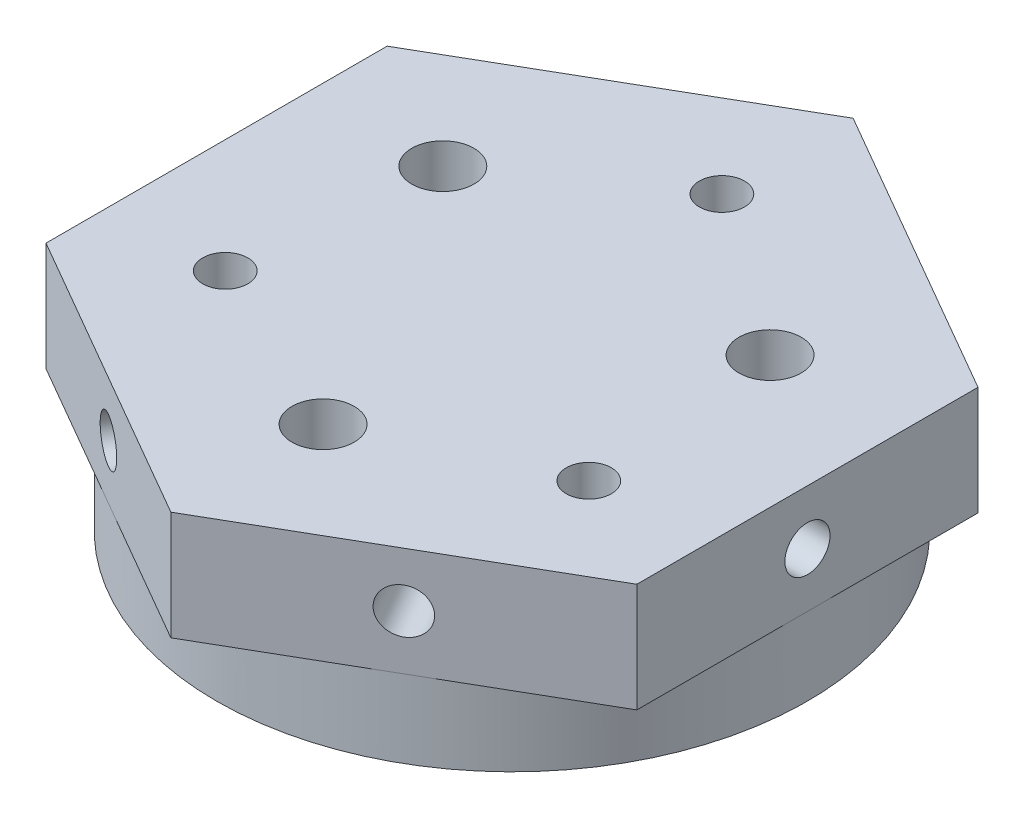
SolidWorks part; units mm, degrees
ref_plane "前视基准面" through (0, 0, 0) normal (0, 0, 1) x (1, 0, 0)
ref_plane "上视基准面" through (0, 0, 0) normal (0, 1, 0) x (1, 0, 0)
ref_plane "右视基准面" through (0, 0, 0) normal (1, 0, 0) x (0, 0, -1)
sketch "草图1" plane through (0, 0, 0) normal (0, 1, 0) x (1, 0, 0)
  line L0 (0, 0) -> (0, 33.3478) construction
  line L1 (0, 0) -> (11.2563, 0) construction
  line B0 (-11.6913, -6.75) -> (0, 0) construction
  line B1 (0, 0) -> (11.6913, -6.75) construction
  line B2 (0, 0) -> (-10.5222, 6.075) construction
  line B3 (10.5222, 6.075) -> (0, 0) construction
  circle B4 centre (0, 0) radius 19
  circle B5 centre (0, 13.5) radius 1.45
  circle B6 centre (0, 0) radius 13.5 construction
  circle B7 centre (-11.6913, -6.75) radius 1.45
  circle B8 centre (11.6913, -6.75) radius 1.45
  circle B9 centre (0, 0) radius 12.15 construction
  circle B10 centre (-10.5222, 6.075) radius 2
  circle B11 centre (0, -12.15) radius 2
  circle B12 centre (10.5222, 6.075) radius 2
  dimension "D4" = 120
  dimension "D5" = 120
  dimension "D7" = 60
  dimension "D9" = 60
sketch_block_instance "块1-1"
sketch_block "块1" parameters "D1"=38, "D2"=27, "D3"=2.9, "D4"=24.3, "D5"=4, "D6"=19.5353, "D8"=4.7251, "D7"=9.7551, "D9"=70.339
extrude "凸台-拉伸1" add sketch "草图1" along normal blind 12
sketch "草图2" plane through (0, 12, 0) normal (0, 1, 0) x (1, 0, 0)
  line L0 (0, 21.9393) -> (0, 0) construction
  line L1 (0, 21.9393) -> (-19, 10.9697)
  line L2 (-19, 10.9697) -> (-19, -10.9697)
  line L3 (-19, -10.9697) -> (0, -21.9393)
  line L4 (0, -21.9393) -> (19, -10.9697)
  line L5 (19, -10.9697) -> (19, 10.9697)
  line L6 (19, 10.9697) -> (0, 21.9393)
  circle A0 centre (0, 0) radius 19 construction
  circle A1 centre (0, 13.5) radius 1.45
  circle A2 centre (0, 13.5) radius 1.45 construction
  circle A3 centre (-10.5222, 6.075) radius 2
  circle A4 centre (-10.5222, 6.075) radius 2 construction
  circle A5 centre (10.5222, 6.075) radius 2
  circle A6 centre (10.5222, 6.075) radius 2 construction
  circle A7 centre (-11.6913, -6.75) radius 1.45
  circle A8 centre (-11.6913, -6.75) radius 1.45 construction
  circle A9 centre (0, -12.15) radius 2
  circle A10 centre (0, -12.15) radius 2 construction
  circle A11 centre (11.6913, -6.75) radius 1.45
  circle A12 centre (11.6913, -6.75) radius 1.45 construction
  dimension "D1" = 38
extrude "凸台-拉伸2" add sketch "草图2" against normal blind 7
sketch "草图3" plane through (9.5, 0, 16.4545) normal (0.5, 0, 0.866) x (0.866, 0, -0.5)
  line L1 (0, 12) -> (0, 5) construction
  line L2 (-10.9697, 12) -> (10.9697, 12) construction
  circle A1 centre (0, 8.5) radius 1.45
  dimension "D1" = 2.9
extrude "切除-拉伸1" cut sketch "草图3" against normal blind 8
sketch "草图4" plane through (-9.5, 0, 16.4545) normal (-0.5, 0, 0.866) x (0.866, 0, 0.5)
  line L0 (0, 5) -> (0, 12) construction
  line L1 (-10.9697, 12) -> (10.9697, 12) construction
  circle A0 centre (0, 8.5) radius 1.45
  dimension "D1" = 2.9
extrude "切除-拉伸2" cut sketch "草图4" against normal blind 8
sketch "草图5" plane through (-19, 0, 0) normal (-1, 0, 0) x (0, 0, 1)
  line L0 (0, 5) -> (0, 12) construction
  line L1 (-10.9697, 12) -> (10.9697, 12) construction
  circle A0 centre (0, 8.5) radius 1.45
  dimension "D1" = 2.9
extrude "切除-拉伸3" cut sketch "草图5" against normal blind 8
sketch "草图6" plane through (19, 0, 0) normal (1, 0, 0) x (0, 0, -1)
  line L0 (0, 12) -> (0, 5) construction
  line L1 (-10.9697, 12) -> (10.9697, 12) construction
  circle A0 centre (0, 8.5) radius 1.45
  dimension "D1" = 2.9
extrude "切除-拉伸4" cut sketch "草图6" against normal blind 8
sketch "草图7" plane through (9.5, 0, -16.4545) normal (0.5, 0, -0.866) x (-0.866, 0, -0.5)
  line L0 (0, 12) -> (0, 5) construction
  line L1 (-10.9697, 12) -> (10.9697, 12) construction
  circle A0 centre (0, 8.5) radius 1.45
  dimension "D1" = 2.9
extrude "切除-拉伸5" cut sketch "草图7" against normal blind 8
